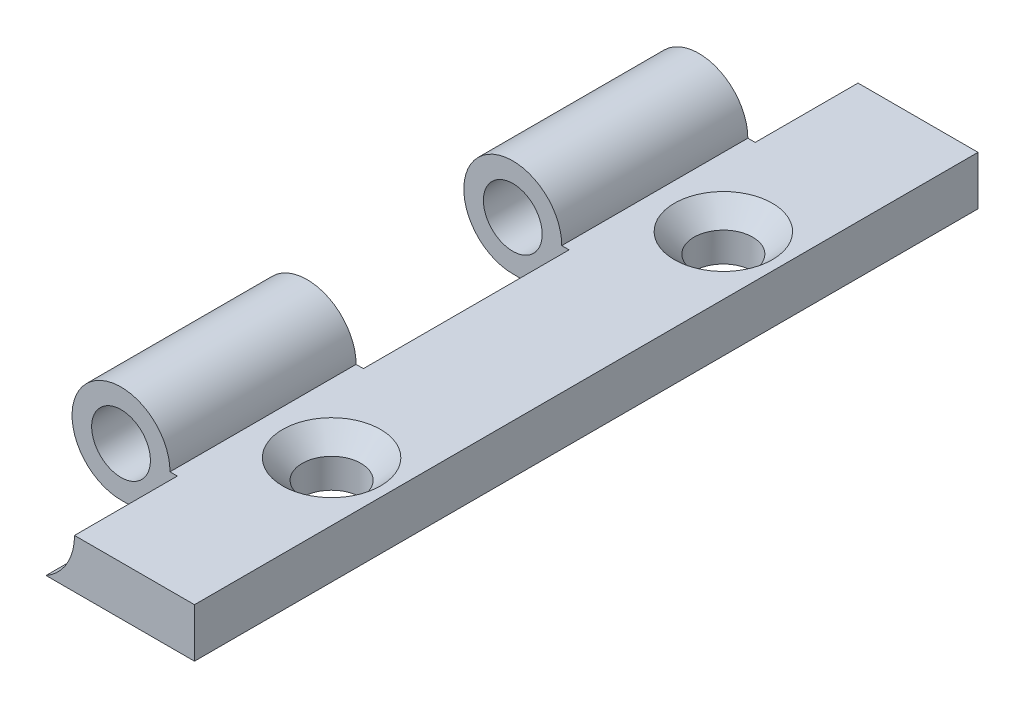
SolidWorks part; units mm, degrees
ref_plane "Front Plane" through (0, 0, 0) normal (0, 0, 1) x (1, 0, 0)
ref_plane "Top Plane" through (0, 0, 0) normal (0, 1, 0) x (1, 0, 0)
ref_plane "Right Plane" through (0, 0, 0) normal (1, 0, 0) x (0, 0, -1)
sketch "Sketch1" plane through (0, 0, 0) normal (0, 1, 0) x (1, 0, 0)
  line L1 (0, 0) -> (-9, 0)
  line L2 (0, 0) -> (0, 40)
  line L3 (0, 40) -> (-9, 40)
  line L4 (-9, 0) -> (-9, 40)
  dimension "D1" = 40
  dimension "D2" = 9
extrude "Boss-Extrude1" add sketch "Sketch1" along normal blind 2.5
sketch "Sketch2" plane through (0, 0, 0) normal (0, 0, 1) x (1, 0, 0)
  circle A0 centre (-9, 2.5) radius 2.5
extrude "Boss-Extrude2" add sketch "Sketch2" against normal blind 9.5 from offset 5.25 offset against normal yes
ref_plane "Plane1" through (0, 0, -20) normal (0, 0, 1) x (1, 0, 0)
sketch "Sketch3" plane through (0, 0, 0) normal (0, 0, 1) x (1, 0, 0)
  circle A0 centre (-9, 2.5) radius 1.5
  dimension "D1" = 3
extrude "Cut-Extrude1" cut sketch "Sketch3" against normal through all
sketch "Sketch4" plane through (0, 0, 0) normal (0, 0, 1) x (1, 0, 0)
  circle A0 centre (-9, 2.5) radius 2.875
  dimension "D1" = 5.75
extrude "Cut-Extrude2" cut sketch "Sketch4" against normal up to surface (5.25 mm away) up to face at (-9.2071, 2.7071, -5.25)
extrude "Cut-Extrude3" cut sketch "Sketch4<2>" along normal up to surface (-14.75 mm away) from surface up to face at (-9.2071, 2.7071, -14.75) starting at plane "Plane1"
sketch "Sketch4<2>" plane through (0, 0, 0) normal (0, 0, 1) x (1, 0, 0) same geometry as "Sketch4"
mirror "Mirror2" about plane through (0, 0, -20) normal (0, 0, 1) of "Cut-Extrude3", "Cut-Extrude2", "Cut-Extrude1", "Boss-Extrude2"
sketch "Sketch5" plane through (0, 2.5, 0) normal (0, 1, 0) x (1, 0, 0)
  line L0 (0, 0) -> (0, 40) construction
  line L1 (-6.125, 0) -> (0, 0) construction
  circle A0 centre (-3, 10) radius 1.5
  dimension "D1" = 3
  dimension "D2" = 3
  dimension "D3" = 10
extrude "Cut-Extrude4" cut sketch "Sketch5" against normal through all
mirror "Mirror3" about plane through (0, 0, -20) normal (0, 0, 1) of "Cut-Extrude4"
chamfer "Chamfer1" distance 1 angle 45 1 edges at (-3, 2.5, -31.5)
chamfer "Chamfer2" distance 1 angle 45 1 edges at (-3, 2.5, -8.5)
